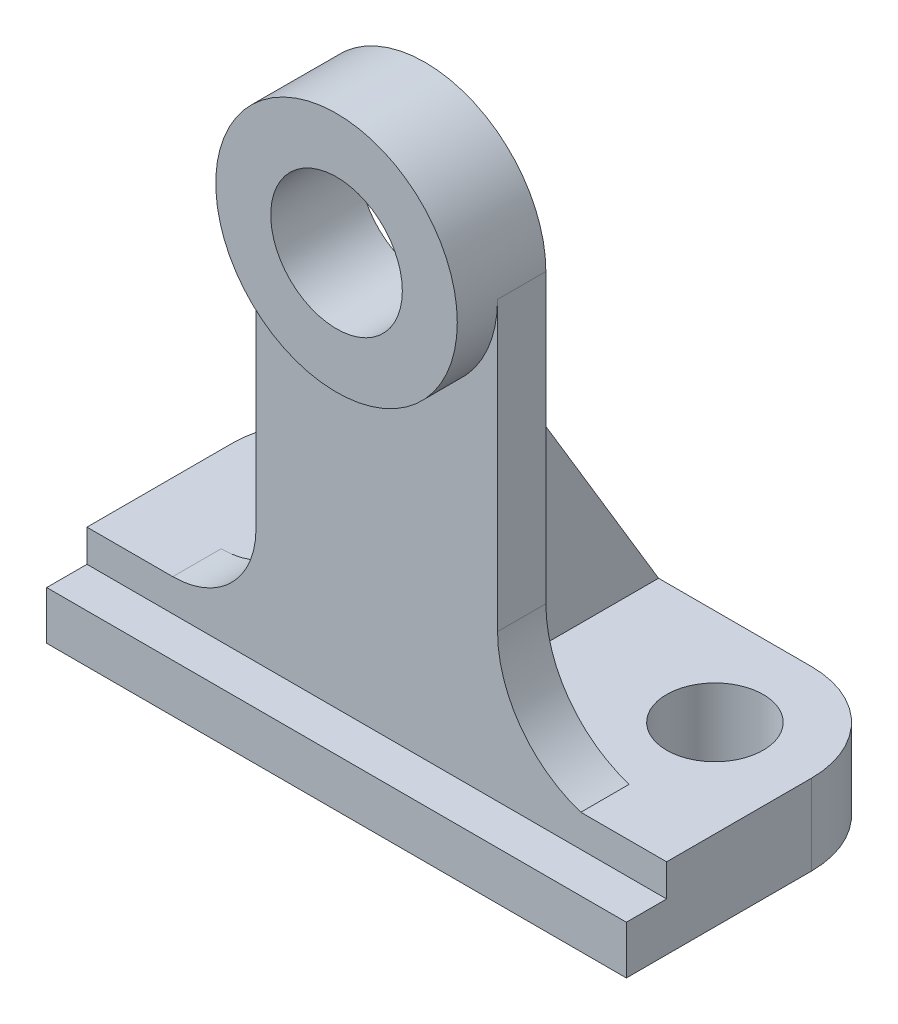
SolidWorks part; units mm, degrees
ref_plane "Front Plane" through (0, 0, 0) normal (0, 0, 1) x (1, 0, 0)
ref_plane "Top Plane" through (0, 0, 0) normal (0, 1, 0) x (1, 0, 0)
ref_plane "Right Plane" through (0, 0, 0) normal (1, 0, 0) x (0, 0, -1)
sketch "Sketch2" plane through (0, 0, 0) normal (1, 0, 0) x (0, 0, -1)
  line L1 (-17.5, 0) -> (-17.5, 6)
  line L2 (-17.5, 6) -> (-12.5, 6)
  line L3 (-12.5, 6) -> (-12.5, 10)
  line L4 (-12.5, 10) -> (17.5, 10)
  line L5 (17.5, 10) -> (17.5, 0)
  line L7 (-17.5, 0) -> (17.5, 0)
  point P0 (0, 0)
  dimension "D1" = 35
  dimension "D2" = 6
  dimension "D3" = 4
  dimension "D4" = 5
extrude "Boss-Extrude1" add sketch "Sketch2" along normal blind 72
sketch "Sketch5" plane through (0, 0, 12.5) normal (0, 0, 1) x (1, 0, 0)
  line L0 (72, 10) -> (0, 10) construction
  line L1 (21, 60) -> (21, 20.3408)
  line L2 (51, 60) -> (51, 24.258)
  line L3 (10.6592, 10) -> (61.3408, 10)
  circle A0 centre (36, 60) radius 8.1732
  arc A1 (21, 60) -> (51, 60) centre (36, 60) cw
  arc A2 (21, 20.3408) -> (10.6592, 10) centre (10.6592, 20.3408) cw
  arc A3 (51, 24.258) -> (61.3408, 10) centre (66, 24.258) ccw
  point P7 (36, 10)
  point P11 (36, 10)
  dimension "D1" = 50
  dimension "D2" = 15
  dimension "D3" = 15
  dimension "15" = 10.3408
  dimension "12" = 16.3464
extrude "Boss-Extrude4" add sketch "Sketch5" against normal blind 6 contours L1 A2 L3 A3 L2 A1
extrude "Cut-Extrude1" cut sketch "Sketch5<3>" against normal blind 6 contours A0
sketch "Sketch5<3>" plane through (0, 0, 12.5) normal (0, 0, 1) x (1, 0, 0) same geometry as "Sketch5"
sketch "Sketch7" plane through (0, 0, 12.5) normal (0, 0, 1) x (1, 0, 0)
  circle A0 centre (36, 60) radius 15
  dimension "D1" = 30
extrude "Boss-Extrude6" add sketch "Sketch7" along normal blind 5
extrude "Cut-Extrude3" cut sketch "Sketch5<6>" along normal blind 5 contours A0
sketch "Sketch5<6>" plane through (0, 0, 12.5) normal (0, 0, 1) x (1, 0, 0) same geometry as "Sketch5"
ref_plane "Plane4" through (36, 0, 0) normal (1, 0, 0) x (0, 0, -1)
sketch "Sketch18" plane through (36, 0, 0) normal (1, 0, 0) x (0, 0, -1)
  line L0 (-6.5, 50) -> (17.5, 10)
  line L1 (-6.5, 60) -> (-6.5, 24.258) construction
  dimension "D1" = 40
rib "Rib6" sketch "Sketch18" sketch "Sketch18" thickness 10 extrusion direction parallel to sketch draft on no parameters "D1"=10
ref_plane "Plane5" through (0, 10, 0) normal (0, 1, 0) x (1, 0, 0)
sketch "Sketch20" plane through (0, 10, 0) normal (0, 1, 0) x (1, 0, 0)
  line L0 (41, 17.5) -> (31, 17.5) construction
  line L1 (0, 17.5) -> (0, -12.5) construction
  line L3 (72, -17.5) -> (0, -17.5) construction
  circle A0 centre (12, 5.5) radius 6
  circle A1 centre (60, 5.5) radius 6
  point P10 (36, 17.5)
  dimension "D1" = 12
  dimension "D2" = 23
  dimension "40" = 48
  dimension "12" = 12
  dimension "D3" = 24
extrude "Cut-Extrude5" cut sketch "Sketch20" against normal through all
fillet "Fillet12" radius 12 2 edges at (72, 5, -17.5) (0, 5, -17.5)
